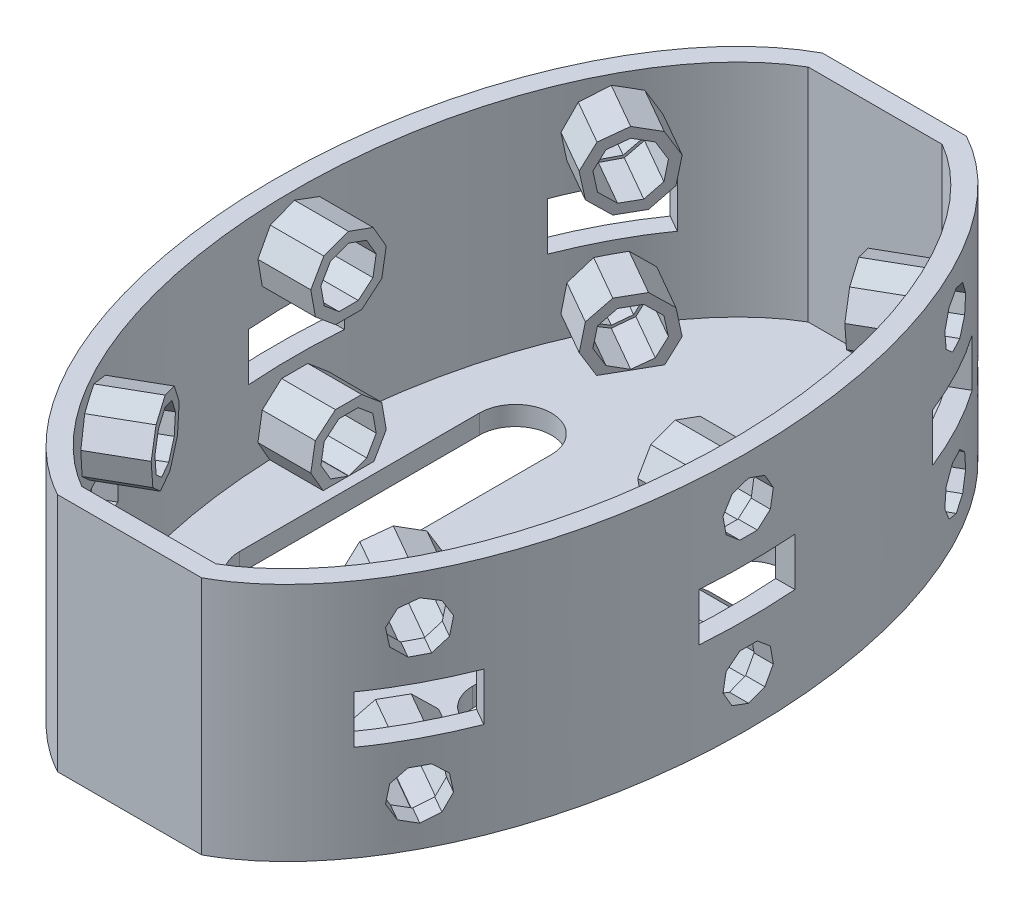
SolidWorks part; units mm, degrees
ref_plane "Front Plane" through (0, 0, 0) normal (0, 0, 1) x (1, 0, 0)
ref_plane "Top Plane" through (0, 0, 0) normal (0, 1, 0) x (1, 0, 0)
ref_plane "Right Plane" through (0, 0, 0) normal (1, 0, 0) x (0, 0, -1)
sketch "Sketch1" plane through (0, 0, 0) normal (0, 1, 0) x (1, 0, 0)
  line L0 (-15, 79.6562) -> (15, 79.6562)
  line L9 (-15, 75.1314) -> (-42.5, 27.5)
  line L10 (-42.5, 27.5) -> (-42.5, -27.5)
  line L16 (15, 75.1314) -> (-15, 75.1314)
  line L17 (-49.2865, 0) -> (49.2865, 0) construction
  line L18 (-15, 75.1314) -> (-15, 79.6562) construction
  line L19 (0, -79.6261) -> (0, -79.6562) construction
  line L20 (-15, 75.1314) -> (-18.7805, 77.3141) construction
  line L21 (-42.5, 27.5) -> (-46.1003, 29.5787) construction
  line L22 (-42.5, 27.5) -> (-46.5452, 27.5) construction
  line L23 (-18.7805, -77.3141) -> (-46.1003, -29.5787) construction
  line L24 (-42.5, -27.5) -> (-46.5452, -27.5) construction
  line L25 (-42.5, -27.5) -> (-46.1003, -29.5787) construction
  line L26 (-15, -75.1314) -> (-18.7805, -77.3141) construction
  line L27 (-15, -75.1314) -> (-15, -79.6562) construction
  line L28 (15, -75.1314) -> (-15, -75.1314)
  line L29 (-15, -75.1314) -> (-42.5, -27.5)
  line L30 (-15, -79.6562) -> (15, -79.6562)
  line L31 (18.7805, 77.3141) -> (46.1003, 29.5787) construction
  line L32 (46.5452, -27.5) -> (46.5452, 27.5) construction
  line L33 (15, -75.1314) -> (15, -79.6562) construction
  line L35 (15, -75.1314) -> (18.7805, -77.3141) construction
  line L36 (42.5, -27.5) -> (46.1003, -29.5787) construction
  line L37 (42.5, -27.5) -> (46.5452, -27.5) construction
  line L38 (18.7805, -77.3141) -> (46.1003, -29.5787) construction
  line L39 (42.5, 27.5) -> (46.5452, 27.5) construction
  line L40 (-46.5452, -27.5) -> (-46.5452, 27.5) construction
  line L41 (-18.7805, 77.3141) -> (-46.1003, 29.5787) construction
  line L42 (0, 79.6562) -> (0, -75.1314) construction
  line L43 (42.5, 27.5) -> (46.1003, 29.5787) construction
  line L44 (15, 75.1314) -> (18.7805, 77.3141) construction
  line L45 (15, 75.1314) -> (15, 79.6562) construction
  line L46 (15, -75.1314) -> (42.5, -27.5)
  line L47 (42.5, 27.5) -> (42.5, -27.5)
  line L48 (15, 75.1314) -> (42.5, 27.5)
  ellipse E0 centre (0, 0) end of major axis (0, 79.6261) minor radius 45.2865
  ellipse E1 centre (0, 0) end of major axis (0, 83.623) minor radius 49.2865 (-15, 79.6562) -> (-15, -79.6562) ccw
  ellipse E2 centre (0, 0) end of major axis (0, 83.623) minor radius 49.2865 (15, 79.6562) -> (15, -79.6562) cw
  point P7 (-46.5452, 0)
  point P15 (-42.5, 0)
  point P16 (45.2865, 0)
  point P42 (0, 79.6261)
  point P46 (-45.2865, 0)
  point P49 (0, 75.1314)
  point P50 (42.5, 0)
  point P51 (46.5452, 0)
  dimension "D1" = 55
  dimension "D3" = 150
extrude "Boss-Extrude2" add sketch "Sketch1" along normal blind 50 contours E1 L30 E2 L0
shell "Shell2" thickness 4 removed face at (0, 50, 0)
ref_plane "Plane2" through (0, 0, 0) normal (0, 1, 0) x (1, 0, 0)
sketch "Sketch3" plane through (0, 0, 0) normal (0, 1, 0) x (1, 0, 0)
  line L9 (-15, 79.6562) -> (15, 79.6562)
  line L10 (-15, 75.1314) -> (-42.5, 27.5)
  line L11 (-42.5, 27.5) -> (-42.5, -27.5)
  line L12 (15, 75.1314) -> (-15, 75.1314)
  line L13 (-49.2865, 0) -> (49.2865, 0) construction
  line L14 (-15, 75.1314) -> (-15, 79.6562) construction
  line L15 (0, -80.445) -> (0, -79.6562) construction
  line L16 (-15, 75.1314) -> (-18.7805, 77.3141) construction
  line L17 (-42.5, 27.5) -> (-46.1003, 29.5787) construction
  line L18 (-42.5, 27.5) -> (-46.5452, 27.5) construction
  line L20 (-18.7805, -77.3141) -> (-46.1003, -29.5787) construction
  line L21 (-42.5, -27.5) -> (-46.5452, -27.5) construction
  line L22 (-42.5, -27.5) -> (-46.1003, -29.5787) construction
  line L23 (-15, -75.1314) -> (-18.7805, -77.3141) construction
  line L24 (-15, -75.1314) -> (-15, -79.6562) construction
  line L27 (15, -75.1314) -> (-15, -75.1314)
  line L28 (-15, -75.1314) -> (-42.5, -27.5)
  line L29 (-15, -79.6562) -> (15, -79.6562)
  line L30 (18.7805, 77.3141) -> (46.1003, 29.5787) construction
  line L31 (46.5452, -27.5) -> (46.5452, 27.5) construction
  line L32 (15, -75.1314) -> (15, -79.6562) construction
  line L33 (15, -75.1314) -> (18.7805, -77.3141) construction
  line L34 (42.5, -27.5) -> (46.1003, -29.5787) construction
  line L35 (42.5, -27.5) -> (46.5452, -27.5) construction
  line L36 (18.7805, -77.3141) -> (46.1003, -29.5787) construction
  line L37 (42.5, 27.5) -> (46.5452, 27.5) construction
  line L38 (-46.5452, -27.5) -> (-46.5452, 27.5) construction
  line L39 (-18.7805, 77.3141) -> (-46.1003, 29.5787) construction
  line L40 (0, 79.6562) -> (0, -75.1314) construction
  line L41 (42.5, 27.5) -> (46.1003, 29.5787) construction
  line L42 (15, 75.1314) -> (18.7805, 77.3141) construction
  line L43 (15, 75.1314) -> (15, 79.6562) construction
  line L44 (15, -75.1314) -> (42.5, -27.5)
  line L45 (42.5, 27.5) -> (42.5, -27.5)
  line L46 (15, 75.1314) -> (42.5, 27.5)
  ellipse E0 centre (0, 0) end of major axis (0, 80.445) minor radius 45.7523
  ellipse E1 centre (0, 0) end of major axis (0, 83.623) minor radius 49.2865 (-15, 79.6562) -> (-15, -79.6562) ccw
  ellipse E3 centre (0, 0) end of major axis (0, 83.623) minor radius 49.2865 (15, 79.6562) -> (15, -79.6562) cw
  point P7 (-46.5452, 0)
  point P14 (-42.5, 0)
  point P15 (45.7523, 0)
  point P57 (0, 80.445)
  point P61 (-45.7523, 0)
  point P64 (0, 75.1314)
  point P65 (42.5, 0)
  point P66 (46.5452, 0)
  dimension "D1" = 55
  dimension "D2" = 150
ref_plane "Plane7" through (0, 4, 0) normal (0, 1, 0) x (1, 0, 0)
sketch "Sketch7" plane through (0, 4, 0) normal (0, 1, 0) x (1, 0, 0)
  line L5 (-24.2865, 25) -> (-24.2865, -25) construction
  line L6 (-16.7865, 25) -> (-16.7865, -25)
  line L10 (-31.7865, 25) -> (-31.7865, -25)
  line L11 (24.2865, 25) -> (24.2865, -25) construction
  line L14 (0, 79.6562) -> (0, -79.6562) construction
  line L15 (-15, 79.6562) -> (15, 79.6562) construction
  line L16 (-15, -79.6562) -> (15, -79.6562) construction
  line L17 (-49.2865, 0) -> (49.2865, 0) construction
  line L18 (16.7865, 25) -> (16.7865, -25)
  line L19 (31.7865, 25) -> (31.7865, -25)
  arc A0 (-16.7865, 25) -> (-31.7865, 25) centre (-24.2865, 25) ccw
  arc A1 (-31.7865, -25) -> (-16.7865, -25) centre (-24.2865, -25) ccw
  arc A2 (16.7865, 25) -> (31.7865, 25) centre (24.2865, 25) cw
  arc A3 (31.7865, -25) -> (16.7865, -25) centre (24.2865, -25) cw
  ellipse E0 centre (0, 0) end of major axis (0, 83.623) minor radius 49.2865 (-15, 79.6562) -> (-15, -79.6562) ccw construction
  ellipse E1 centre (0, 0) end of major axis (0, 83.623) minor radius 49.2865 (15, -79.6562) -> (15, 79.6562) ccw construction
  point P1 (-24.2865, 0)
  point P7 (0, 0)
  point P10 (24.2865, 0)
  dimension "D1" = 25
extrude "Cut-Extrude4" cut sketch "Sketch7" against normal blind 10
sketch3d "3DSketch1"
  line L0 (-15, 0, -79.6562) -> (-15, 50, -79.6562)
  line L1 (-18.7805, 0, -77.3141) -> (-18.7805, 50, -77.3141)
  line L2 (-46.1003, 0, -29.5787) -> (-46.1003, 50, -29.5787)
  line L3 (-46.5452, 0, -27.5) -> (-46.5452, 50, -27.5)
  line L4 (-46.5452, 0, 27.5) -> (-46.5452, 50, 27.5)
  line L5 (-46.1003, 0, 29.5787) -> (-46.1003, 50, 29.5787)
  line L6 (-18.7805, 0, 77.3141) -> (-18.7805, 50, 77.3141)
  line L7 (-15, 0, 79.6562) -> (-15, 50, 79.6562)
  line L8 (15, 0, 79.6562) -> (15, 50, 79.6562)
  line L9 (18.7805, 0, 77.3141) -> (18.7805, 50, 77.3141)
  line L11 (46.1003, 0, 29.5787) -> (46.1003, 50, 29.5787)
  line L12 (46.5452, 0, -27.5) -> (46.5452, 50, -27.5)
  line L13 (46.1003, 0, -29.5787) -> (46.1003, 50, -29.5787)
  line L14 (46.5452, 0, 27.5) -> (46.5452, 50, 27.5)
  line L15 (18.7805, 0, -77.3141) -> (18.7805, 50, -77.3141)
  line L16 (15, 0, -79.6562) -> (15, 50, -79.6562)
  line L17 (15, 50, -79.6562) -> (15, 0, -79.6562) construction
  spline S0 degree 3 poles (-15, 50, -79.6562) (-70.5999, 50, -49.5163) (-70.5999, 50, 49.5163) (-15, 50, 79.6562) knots 0 0 0 0 1 1 1 1 weights 1 0.536229 0.536229 1 construction
  spline S1 degree 3 poles (15, 50, -79.6562) (70.5999, 50, -49.5163) (70.5999, 50, 49.5163) (15, 50, 79.6562) knots 0 0 0 0 1 1 1 1 weights 1 0.536229 0.536229 1 construction
ref_plane "Plane8" through (-47.4776, 0, -27.1722) normal (0.8679, 0, 0.4967) x (0.4967, 0, -0.8679)
ref_plane "Plane9" through (-46.5452, 0, 0) normal (1, 0, 0) x (0, 0, -1)
ref_plane "Plane10" through (-47.4776, 0, 27.1722) normal (0.8679, 0, -0.4967) x (-0.4967, 0, -0.8679)
sketch "Sketch8" plane through (-47.4776, 0, -27.1722) normal (0.8679, 0, 0.4967) x (0.4967, 0, -0.8679)
  line L0 (57.7731, 50) -> (2.7727, 50) construction
  line L1 (2.7727, 50) -> (2.7727, 0) construction
  line L2 (2.7727, 0) -> (57.7731, 0) construction
  line L3 (57.7731, 0) -> (57.7731, 50) construction
  line L4 (30.2729, 50) -> (30.2729, 0) construction
  line L6 (40.2729, 20) -> (20.2729, 20)
  line L7 (2.7727, 25) -> (57.7731, 25) construction
  line L8 (40.2729, 20) -> (40.2729, 30)
  line L9 (40.2729, 30) -> (20.2729, 30)
  line L10 (20.2729, 20) -> (20.2729, 30)
  line L11 (40.2729, 20) -> (20.2729, 30) construction
  line L12 (40.2729, 30) -> (20.2729, 20) construction
  line L13 (30.2729, 45.3209) -> (26.8527, 44.076)
  line L14 (26.8527, 44.076) -> (25.0328, 40.924)
  line L15 (25.0328, 40.924) -> (25.6649, 37.3396)
  line L16 (25.6649, 37.3396) -> (28.453, 35)
  line L17 (28.453, 35) -> (32.0927, 35)
  line L18 (32.0927, 35) -> (34.8809, 37.3396)
  line L19 (34.8809, 37.3396) -> (35.5129, 40.924)
  line L20 (35.5129, 40.924) -> (33.6931, 44.076)
  line L21 (33.6931, 44.076) -> (30.2729, 45.3209)
  line L22 (26.8527, 5.924) -> (30.2729, 4.6791)
  line L23 (30.2729, 4.6791) -> (33.6931, 5.924)
  line L24 (33.6931, 5.924) -> (35.5129, 9.076)
  line L25 (35.5129, 9.076) -> (34.8809, 12.6604)
  line L26 (34.8809, 12.6604) -> (32.0927, 15)
  line L27 (32.0927, 15) -> (28.453, 15)
  line L28 (28.453, 15) -> (25.6649, 12.6604)
  line L29 (25.6649, 12.6604) -> (25.0328, 9.076)
  line L30 (25.0328, 9.076) -> (26.8527, 5.924)
  circle A0 centre (30.2729, 40) radius 5 construction
  circle A1 centre (30.2729, 10) radius 5 construction
  point P10 (30.2729, 25)
  dimension "D1" = 10
  dimension "D2" = 10
extrude "Cut-Extrude5" cut sketch "Sketch8" along normal blind 10 and the other way blind 10
sketch "Sketch9" plane through (-46.5452, 0, 0) normal (1, 0, 0) x (0, 0, -1)
  line L0 (27.5, 50) -> (-27.5, 50) construction
  line L1 (-27.5, 50) -> (-27.5, 0) construction
  line L2 (-27.5, 0) -> (27.5, 0) construction
  line L3 (27.5, 0) -> (27.5, 50) construction
  line L4 (0, 50) -> (0, 0) construction
  line L5 (27.5, 25) -> (-27.5, 25) construction
  line L7 (10, 30) -> (-10, 30)
  line L8 (10, 30) -> (10, 20)
  line L9 (10, 20) -> (-10, 20)
  line L10 (-10, 30) -> (-10, 20)
  line L11 (10, 30) -> (-10, 20) construction
  line L12 (10, 20) -> (-10, 30) construction
  line L13 (-1.8199, 35) -> (1.8199, 35)
  line L14 (1.8199, 35) -> (4.608, 37.3396)
  line L15 (4.608, 37.3396) -> (5.2401, 40.924)
  line L16 (5.2401, 40.924) -> (3.4202, 44.076)
  line L17 (3.4202, 44.076) -> (0, 45.3209)
  line L18 (0, 45.3209) -> (-3.4202, 44.076)
  line L19 (-3.4202, 44.076) -> (-5.2401, 40.924)
  line L20 (-5.2401, 40.924) -> (-4.608, 37.3396)
  line L21 (-4.608, 37.3396) -> (-1.8199, 35)
  line L22 (0, 4.6791) -> (3.4202, 5.924)
  line L23 (3.4202, 5.924) -> (5.2401, 9.076)
  line L24 (5.2401, 9.076) -> (4.608, 12.6604)
  line L25 (4.608, 12.6604) -> (1.8199, 15)
  line L26 (1.8199, 15) -> (-1.8199, 15)
  line L27 (-1.8199, 15) -> (-4.608, 12.6604)
  line L28 (-4.608, 12.6604) -> (-5.2401, 9.076)
  line L29 (-5.2401, 9.076) -> (-3.4202, 5.924)
  line L30 (-3.4202, 5.924) -> (0, 4.6791)
  circle A0 centre (0, 40) radius 5 construction
  circle A1 centre (0, 10) radius 5 construction
  point P13 (0, 25)
  dimension "D1" = 10
  dimension "D2" = 10
extrude "Cut-Extrude6" cut sketch "Sketch9" against normal blind 10 and the other way blind 10
sketch "Sketch11" plane through (-47.4776, 0, 27.1722) normal (0.8679, 0, -0.4967) x (-0.4967, 0, -0.8679)
  line L0 (-2.7727, 50) -> (-57.7731, 50) construction
  line L1 (-57.7731, 50) -> (-57.7731, 0) construction
  line L2 (-57.7731, 0) -> (-2.7727, 0) construction
  line L3 (-2.7727, 0) -> (-2.7727, 50) construction
  line L4 (-30.2729, 50) -> (-30.2729, 0) construction
  line L5 (-2.7727, 25) -> (-57.7731, 25) construction
  line L7 (-40.2729, 20) -> (-20.2729, 20)
  line L8 (-40.2729, 20) -> (-40.2729, 30)
  line L9 (-40.2729, 30) -> (-20.2729, 30)
  line L10 (-20.2729, 20) -> (-20.2729, 30)
  line L11 (-40.2729, 20) -> (-20.2729, 30) construction
  line L12 (-40.2729, 30) -> (-20.2729, 20) construction
  line L13 (-34.8809, 37.3396) -> (-32.0927, 35)
  line L14 (-32.0927, 35) -> (-28.453, 35)
  line L15 (-28.453, 35) -> (-25.6649, 37.3396)
  line L16 (-25.6649, 37.3396) -> (-25.0328, 40.924)
  line L17 (-25.0328, 40.924) -> (-26.8527, 44.076)
  line L18 (-26.8527, 44.076) -> (-30.2729, 45.3209)
  line L19 (-30.2729, 45.3209) -> (-33.6931, 44.076)
  line L20 (-33.6931, 44.076) -> (-35.5129, 40.924)
  line L21 (-35.5129, 40.924) -> (-34.8809, 37.3396)
  line L22 (-35.5129, 9.076) -> (-33.6931, 5.924)
  line L23 (-33.6931, 5.924) -> (-30.2729, 4.6791)
  line L24 (-30.2729, 4.6791) -> (-26.8527, 5.924)
  line L25 (-26.8527, 5.924) -> (-25.0328, 9.076)
  line L26 (-25.0328, 9.076) -> (-25.6649, 12.6604)
  line L27 (-25.6649, 12.6604) -> (-28.453, 15)
  line L28 (-28.453, 15) -> (-32.0927, 15)
  line L29 (-32.0927, 15) -> (-34.8809, 12.6604)
  line L30 (-34.8809, 12.6604) -> (-35.5129, 9.076)
  circle A0 centre (-30.2729, 40) radius 5 construction
  circle A1 centre (-30.2729, 10) radius 5 construction
  point P12 (-30.2729, 25)
  dimension "D1" = 10
  dimension "D2" = 10
extrude "Cut-Extrude7" cut sketch "Sketch11" against normal blind 10 and the other way blind 10
mirror "Mirror1" about plane through (0, 0, 0) normal (1, 0, 0) of "Cut-Extrude7", "Cut-Extrude6", "Cut-Extrude5"
sketch "Sketch12" plane through (-47.4776, 0, 27.1722) normal (0.8679, 0, -0.4967) x (-0.4967, 0, -0.8679)
  line L36 (-2.7727, 50) -> (-57.7731, 50) construction
  line L37 (-57.7731, 50) -> (-57.7731, 0) construction
  line L38 (-57.7731, 0) -> (-2.7727, 0) construction
  line L39 (-2.7727, 0) -> (-2.7727, 50) construction
  line L40 (-30.2729, 50) -> (-30.2729, 0) construction
  line L41 (-26.8527, 44.076) -> (-33.4868, 36.1698) construction
  line L42 (-33.6931, 44.076) -> (-27.0589, 36.1698) construction
  line L43 (-25.0328, 40.924) -> (-35.1969, 39.1318) construction
  line L44 (-28.453, 15) -> (-31.983, 5.3015) construction
  line L45 (-37.1849, 36.0093) -> (-33.0027, 32.5)
  line L46 (-33.0027, 32.5) -> (-27.5431, 32.5)
  line L47 (-27.5431, 32.5) -> (-23.3608, 36.0093)
  line L48 (-23.3608, 36.0093) -> (-22.4128, 41.3859)
  line L49 (-22.4128, 41.3859) -> (-25.1426, 46.1141)
  line L50 (-25.1426, 46.1141) -> (-30.2729, 47.9813)
  line L51 (-30.2729, 47.9813) -> (-35.4032, 46.1141)
  line L52 (-35.4032, 46.1141) -> (-38.133, 41.3859)
  line L53 (-38.133, 41.3859) -> (-37.1849, 36.0093)
  line L54 (-25.6649, 12.6604) -> (-34.603, 7.5) construction
  line L55 (-25.0328, 9.076) -> (-35.1969, 10.8682) construction
  line L57 (-35.4032, 3.8859) -> (-30.2729, 2.0187)
  line L58 (-30.2729, 2.0187) -> (-25.1426, 3.8859)
  line L59 (-25.1426, 3.8859) -> (-22.4128, 8.6141)
  line L60 (-22.4128, 8.6141) -> (-23.3608, 13.9907)
  line L61 (-23.3608, 13.9907) -> (-27.5431, 17.5)
  line L62 (-27.5431, 17.5) -> (-33.0027, 17.5)
  line L63 (-33.0027, 17.5) -> (-37.1849, 13.9907)
  line L64 (-37.1849, 13.9907) -> (-38.133, 8.6141)
  line L65 (-38.133, 8.6141) -> (-35.4032, 3.8859)
  line L66 (-26.5107, 44.4836) -> (-30.2729, 45.853)
  line L67 (-30.2729, 45.853) -> (-34.0351, 44.4836)
  line L68 (-34.0351, 44.4836) -> (-36.0369, 41.0164)
  line L69 (-36.0369, 41.0164) -> (-35.3417, 37.0735)
  line L70 (-35.3417, 37.0735) -> (-32.2747, 34.5)
  line L71 (-32.2747, 34.5) -> (-28.271, 34.5)
  line L72 (-28.271, 34.5) -> (-25.204, 37.0735)
  line L73 (-25.204, 37.0735) -> (-24.5088, 41.0164)
  line L74 (-24.5088, 41.0164) -> (-26.5107, 44.4836)
  line L75 (-34.0351, 5.5164) -> (-30.2729, 4.147)
  line L76 (-30.2729, 4.147) -> (-26.5107, 5.5164)
  line L77 (-26.5107, 5.5164) -> (-24.5088, 8.9836)
  line L78 (-24.5088, 8.9836) -> (-25.204, 12.9265)
  line L79 (-25.204, 12.9265) -> (-28.271, 15.5)
  line L80 (-28.271, 15.5) -> (-32.2747, 15.5)
  line L81 (-32.2747, 15.5) -> (-35.3417, 12.9265)
  line L82 (-35.3417, 12.9265) -> (-36.0369, 8.9836)
  line L83 (-36.0369, 8.9836) -> (-34.0351, 5.5164)
  circle A0 centre (-30.2729, 40) radius 7.5 construction
  circle A1 centre (-30.2729, 10) radius 7.5 construction
  circle A2 centre (-30.2729, 40) radius 5.5 construction
  circle A3 centre (-30.2729, 10) radius 5.5 construction
extrude "Boss-Extrude4" add sketch "Sketch12" along normal blind 10 and the other way blind 3
sketch "Sketch13" plane through (-47.4776, 0, -27.1722) normal (0.8679, 0, 0.4967) x (0.4967, 0, -0.8679)
  line L0 (57.7731, 50) -> (2.7727, 50) construction
  line L1 (2.7727, 50) -> (2.7727, 0) construction
  line L2 (2.7727, 0) -> (57.7731, 0) construction
  line L3 (57.7731, 0) -> (57.7731, 50) construction
  line L4 (30.2729, 50) -> (30.2729, 0) construction
  line L33 (33.6931, 44.076) -> (27.0589, 36.1698) construction
  line L34 (34.8809, 37.3396) -> (25.9427, 42.5) construction
  line L35 (35.5129, 40.924) -> (25.3488, 39.1318) construction
  line L36 (32.0927, 15) -> (28.5628, 5.3015) construction
  line L37 (35.5129, 9.076) -> (25.3488, 10.8682) construction
  line L39 (30.2729, 4.147) -> (34.0351, 5.5164)
  line L40 (34.0351, 5.5164) -> (36.0369, 8.9836)
  line L41 (36.0369, 8.9836) -> (35.3417, 12.9265)
  line L42 (35.3417, 12.9265) -> (32.2747, 15.5)
  line L43 (32.2747, 15.5) -> (28.271, 15.5)
  line L44 (28.271, 15.5) -> (25.204, 12.9265)
  line L45 (25.204, 12.9265) -> (24.5088, 8.9836)
  line L46 (24.5088, 8.9836) -> (26.5107, 5.5164)
  line L47 (26.5107, 5.5164) -> (30.2729, 4.147)
  line L48 (25.1426, 3.8859) -> (30.2729, 2.0187)
  line L49 (30.2729, 2.0187) -> (35.4032, 3.8859)
  line L50 (35.4032, 3.8859) -> (38.133, 8.6141)
  line L51 (38.133, 8.6141) -> (37.1849, 13.9907)
  line L52 (37.1849, 13.9907) -> (33.0027, 17.5)
  line L53 (33.0027, 17.5) -> (27.5431, 17.5)
  line L54 (27.5431, 17.5) -> (23.3608, 13.9907)
  line L55 (23.3608, 13.9907) -> (22.4128, 8.6141)
  line L56 (22.4128, 8.6141) -> (25.1426, 3.8859)
  line L57 (28.271, 34.4843) -> (32.2747, 34.4843)
  line L58 (32.2747, 34.4843) -> (35.3417, 37.0578)
  line L59 (35.3417, 37.0578) -> (36.0369, 41.0006)
  line L60 (36.0369, 41.0006) -> (34.0351, 44.4679)
  line L61 (34.0351, 44.4679) -> (30.2729, 45.8373)
  line L62 (30.2729, 45.8373) -> (26.5107, 44.4679)
  line L63 (26.5107, 44.4679) -> (24.5088, 41.0006)
  line L64 (24.5088, 41.0006) -> (25.204, 37.0578)
  line L65 (25.204, 37.0578) -> (28.271, 34.4843)
  line L66 (27.5431, 32.4843) -> (33.0027, 32.4843)
  line L67 (33.0027, 32.4843) -> (37.1849, 35.9936)
  line L68 (37.1849, 35.9936) -> (38.133, 41.3702)
  line L69 (38.133, 41.3702) -> (35.4032, 46.0983)
  line L70 (35.4032, 46.0983) -> (30.2729, 47.9656)
  line L71 (30.2729, 47.9656) -> (25.1426, 46.0983)
  line L72 (25.1426, 46.0983) -> (22.4128, 41.3702)
  line L73 (22.4128, 41.3702) -> (23.3608, 35.9936)
  line L74 (23.3608, 35.9936) -> (27.5431, 32.4843)
  circle A0 centre (30.2729, 10) radius 5.5 construction
  circle A1 centre (30.2729, 10) radius 7.5 construction
  circle A2 centre (30.2729, 39.9843) radius 5.5 construction
  circle A3 centre (30.2729, 39.9843) radius 7.5 construction
extrude "Boss-Extrude5" add sketch "Sketch13" along normal blind 10 and the other way blind 3
sketch "Sketch14" plane through (-46.5452, 0, 0) normal (1, 0, 0) x (0, 0, -1)
  line L0 (27.5, 50) -> (-27.5, 50) construction
  line L1 (-27.5, 50) -> (-27.5, 0) construction
  line L2 (-27.5, 0) -> (27.5, 0) construction
  line L3 (27.5, 0) -> (27.5, 50) construction
  line L4 (0, 50) -> (0, 45.3209) construction
  line L41 (0, 4.6791) -> (0, 0) construction
  line L42 (0, 35) -> (0, 15) construction
  line L43 (0, 45.3209) -> (0, 35) construction
  line L44 (0, 15) -> (0, 4.6791) construction
  line L46 (-5.0608, 37.2201) -> (-1.9868, 34.655)
  line L47 (-1.9868, 34.655) -> (2.0169, 34.6659)
  line L48 (2.0169, 34.6659) -> (5.0768, 37.2479)
  line L49 (5.0768, 37.2479) -> (5.7613, 41.1926)
  line L50 (5.7613, 41.1926) -> (3.7499, 44.6544)
  line L51 (3.7499, 44.6544) -> (-0.016, 46.0134)
  line L52 (-0.016, 46.0134) -> (-3.7745, 44.6338)
  line L53 (-3.7745, 44.6338) -> (-5.7668, 41.161)
  line L54 (-5.7668, 41.161) -> (-5.0608, 37.2201)
  line L55 (-6.9011, 36.1509) -> (-2.7092, 32.653)
  line L56 (-2.7092, 32.653) -> (2.7503, 32.6679)
  line L57 (2.7503, 32.6679) -> (6.9229, 36.1887)
  line L58 (6.9229, 36.1887) -> (7.8563, 41.5679)
  line L59 (7.8563, 41.5679) -> (5.1135, 46.2885)
  line L60 (5.1135, 46.2885) -> (-0.0219, 48.1417)
  line L61 (-0.0219, 48.1417) -> (-5.147, 46.2604)
  line L62 (-5.147, 46.2604) -> (-7.8638, 41.5249)
  line L63 (-7.8638, 41.5249) -> (-6.9011, 36.1509)
  line L64 (-7.8601, 8.4537) -> (-5.1303, 3.7255)
  line L65 (-5.1303, 3.7255) -> (-0.0001, 1.8582)
  line L66 (-0.0001, 1.8582) -> (5.1303, 3.7255)
  line L67 (5.1303, 3.7255) -> (7.8601, 8.4536)
  line L68 (7.8601, 8.4536) -> (6.9121, 13.8302)
  line L69 (6.9121, 13.8302) -> (2.7298, 17.3395)
  line L70 (2.7298, 17.3395) -> (-2.7297, 17.3396)
  line L71 (-2.7297, 17.3396) -> (-6.912, 13.8303)
  line L72 (-6.912, 13.8303) -> (-7.8601, 8.4537)
  line L73 (-3.7429, 5.3398) -> (0.0251, 3.9866)
  line L74 (0.0251, 3.9866) -> (3.7815, 5.3721)
  line L75 (3.7815, 5.3721) -> (5.7684, 8.848)
  line L76 (5.7684, 8.848) -> (5.0562, 12.7878)
  line L77 (5.0562, 12.7878) -> (1.9782, 15.3481)
  line L78 (1.9782, 15.3481) -> (-2.0254, 15.3309)
  line L79 (-2.0254, 15.3309) -> (-5.0814, 12.7442)
  line L80 (-5.0814, 12.7442) -> (-5.7596, 8.7984)
  line L81 (-5.7596, 8.7984) -> (-3.7429, 5.3398)
  circle A0 centre (0, 40.1604) radius 5.5 construction
  circle A1 centre (0, 40.1604) radius 7.5 construction
  circle A2 centre (0, 9.8396) radius 7.5 construction
  circle A3 centre (0, 9.8396) radius 5.5 construction
extrude "Boss-Extrude6" add sketch "Sketch14" along normal blind 12.5 and the other way blind 2
ref_plane "Plane11" through (47.4776, 0, 27.1722) normal (-0.8679, 0, -0.4967) x (-0.4967, 0, 0.8679)
ref_plane "Plane12" through (46.5452, 0, 0) normal (-1, 0, 0) x (0, 0, 1)
ref_plane "Plane13" through (47.4776, 0, -27.1722) normal (0.8679, 0, -0.4967) x (-0.4967, 0, -0.8679)
sketch "Sketch15" plane through (47.4776, 0, 27.1722) normal (-0.8679, 0, -0.4967) x (-0.4967, 0, 0.8679)
  line L12 (30.2729, 45.3209) -> (30.2729, 35) construction
  line L13 (30.2729, 15) -> (30.2729, 4.6791) construction
  line L14 (30.2729, 15) -> (30.2729, 35) construction
  line L15 (30.2729, 45.3209) -> (30.2729, 49.8304) construction
  line L16 (30.2729, 4.6791) -> (30.2729, 0) construction
  line L18 (25.204, 37.234) -> (28.271, 34.6604)
  line L19 (28.271, 34.6604) -> (32.2747, 34.6604)
  line L20 (32.2747, 34.6604) -> (35.3417, 37.234)
  line L21 (35.3417, 37.234) -> (36.0369, 41.1768)
  line L22 (36.0369, 41.1768) -> (34.0351, 44.6441)
  line L23 (34.0351, 44.6441) -> (30.2729, 46.0134)
  line L24 (30.2729, 46.0134) -> (26.5107, 44.6441)
  line L25 (26.5107, 44.6441) -> (24.5088, 41.1768)
  line L26 (24.5088, 41.1768) -> (25.204, 37.234)
  line L27 (23.3608, 36.1698) -> (27.5431, 32.6604)
  line L28 (27.5431, 32.6604) -> (33.0027, 32.6604)
  line L29 (33.0027, 32.6604) -> (37.1849, 36.1698)
  line L30 (37.1849, 36.1698) -> (38.133, 41.5464)
  line L31 (38.133, 41.5464) -> (35.4032, 46.2745)
  line L32 (35.4032, 46.2745) -> (30.2729, 48.1418)
  line L33 (30.2729, 48.1418) -> (25.1426, 46.2745)
  line L34 (25.1426, 46.2745) -> (22.4128, 41.5464)
  line L35 (22.4128, 41.5464) -> (23.3608, 36.1698)
  line L36 (24.5088, 8.8232) -> (26.5107, 5.3559)
  line L37 (26.5107, 5.3559) -> (30.2729, 3.9866)
  line L38 (30.2729, 3.9866) -> (34.0351, 5.3559)
  line L39 (34.0351, 5.3559) -> (36.0369, 8.8232)
  line L40 (36.0369, 8.8232) -> (35.3417, 12.766)
  line L41 (35.3417, 12.766) -> (32.2747, 15.3396)
  line L42 (32.2747, 15.3396) -> (28.271, 15.3396)
  line L43 (28.271, 15.3396) -> (25.204, 12.766)
  line L44 (25.204, 12.766) -> (24.5088, 8.8232)
  line L45 (22.4128, 8.4536) -> (25.1426, 3.7255)
  line L46 (25.1426, 3.7255) -> (30.2729, 1.8582)
  line L47 (30.2729, 1.8582) -> (35.4032, 3.7255)
  line L48 (35.4032, 3.7255) -> (38.133, 8.4536)
  line L49 (38.133, 8.4536) -> (37.1849, 13.8302)
  line L50 (37.1849, 13.8302) -> (33.0027, 17.3396)
  line L51 (33.0027, 17.3396) -> (27.5431, 17.3396)
  line L52 (27.5431, 17.3396) -> (23.3608, 13.8302)
  line L53 (23.3608, 13.8302) -> (22.4128, 8.4536)
  circle A0 centre (30.2729, 40.1604) radius 5.5 construction
  circle A1 centre (30.2729, 40.1604) radius 7.5 construction
  circle A2 centre (30.2729, 9.8396) radius 5.5 construction
  circle A3 centre (30.2729, 9.8396) radius 7.5 construction
  point P1 (0, 0)
  point P2 (0, 0)
  point P36 (0, 0)
  point P57 (0, 0)
extrude "Boss-Extrude7" add sketch "Sketch15" along normal blind 10 and the other way blind 3
sketch "Sketch16" plane through (46.5452, 0, 0) normal (-1, 0, 0) x (0, 0, 1)
  line L12 (0, 45.3209) -> (0, 35) construction
  line L13 (0, 4.6791) -> (0, 15) construction
  line L14 (0, 35) -> (0, 15) construction
  line L15 (0, 45.3209) -> (0, 49.3861) construction
  line L16 (0, 4.6791) -> (0, -0.5773) construction
  line L18 (-5.7641, 8.8232) -> (-3.7622, 5.3559)
  line L19 (-3.7622, 5.3559) -> (0, 3.9866)
  line L20 (0, 3.9866) -> (3.7622, 5.3559)
  line L21 (3.7622, 5.3559) -> (5.7641, 8.8232)
  line L22 (5.7641, 8.8232) -> (5.0688, 12.766)
  line L23 (5.0688, 12.766) -> (2.0018, 15.3396)
  line L24 (2.0018, 15.3396) -> (-2.0018, 15.3396)
  line L25 (-2.0018, 15.3396) -> (-5.0688, 12.766)
  line L26 (-5.0688, 12.766) -> (-5.7641, 8.8232)
  line L27 (-7.8601, 8.4536) -> (-5.1303, 3.7255)
  line L28 (-5.1303, 3.7255) -> (0, 1.8582)
  line L29 (0, 1.8582) -> (5.1303, 3.7255)
  line L30 (5.1303, 3.7255) -> (7.8601, 8.4536)
  line L31 (7.8601, 8.4536) -> (6.912, 13.8302)
  line L32 (6.912, 13.8302) -> (2.7298, 17.3396)
  line L33 (2.7298, 17.3396) -> (-2.7298, 17.3396)
  line L34 (-2.7298, 17.3396) -> (-6.912, 13.8302)
  line L35 (-6.912, 13.8302) -> (-7.8601, 8.4536)
  line L36 (-6.912, 36.1698) -> (-2.7298, 32.6604)
  line L37 (-2.7298, 32.6604) -> (2.7298, 32.6604)
  line L38 (2.7298, 32.6604) -> (6.912, 36.1698)
  line L39 (6.912, 36.1698) -> (7.8601, 41.5464)
  line L40 (7.8601, 41.5464) -> (5.1303, 46.2745)
  line L41 (5.1303, 46.2745) -> (0, 48.1418)
  line L42 (0, 48.1418) -> (-5.1303, 46.2745)
  line L43 (-5.1303, 46.2745) -> (-7.8601, 41.5464)
  line L44 (-7.8601, 41.5464) -> (-6.912, 36.1698)
  line L45 (-5.0688, 37.234) -> (-2.0018, 34.6604)
  line L46 (-2.0018, 34.6604) -> (2.0018, 34.6604)
  line L47 (2.0018, 34.6604) -> (5.0688, 37.234)
  line L48 (5.0688, 37.234) -> (5.7641, 41.1768)
  line L49 (5.7641, 41.1768) -> (3.7622, 44.6441)
  line L50 (3.7622, 44.6441) -> (0, 46.0134)
  line L51 (0, 46.0134) -> (-3.7622, 44.6441)
  line L52 (-3.7622, 44.6441) -> (-5.7641, 41.1768)
  line L53 (-5.7641, 41.1768) -> (-5.0688, 37.234)
  circle A0 centre (0, 9.8396) radius 5.5 construction
  circle A1 centre (0, 9.8396) radius 7.5 construction
  circle A2 centre (0, 40.1604) radius 7.5 construction
  circle A3 centre (0, 40.1604) radius 5.5 construction
  point P37 (0, 0)
  point P58 (0, 0)
  point P59 (0, 0)
  point P60 (0, 0)
extrude "Boss-Extrude8" add sketch "Sketch16" along normal blind 12.5 and the other way blind 2
sketch "Sketch17" plane through (47.4776, 0, -27.1722) normal (0.8679, 0, -0.4967) x (-0.4967, 0, -0.8679)
  line L12 (30.2729, 4.6791) -> (30.2729, 15) construction
  line L13 (30.2729, 15) -> (30.2729, 35) construction
  line L14 (30.2729, 35) -> (30.2729, 45.3209) construction
  line L15 (30.2729, 45.3209) -> (30.2729, 50) construction
  line L16 (61.6836, 50) -> (-76.5951, 50) construction
  line L17 (30.2729, 4.6791) -> (30.2729, 0) construction
  line L18 (-76.5951, 0) -> (61.6836, 0) construction
  line L20 (36.0369, 8.8232) -> (35.3417, 12.766)
  line L21 (35.3417, 12.766) -> (32.2747, 15.3396)
  line L22 (32.2747, 15.3396) -> (28.271, 15.3396)
  line L23 (28.271, 15.3396) -> (25.204, 12.766)
  line L24 (25.204, 12.766) -> (24.5088, 8.8232)
  line L25 (24.5088, 8.8232) -> (26.5107, 5.3559)
  line L26 (26.5107, 5.3559) -> (30.2729, 3.9866)
  line L27 (30.2729, 3.9866) -> (34.0351, 5.3559)
  line L28 (34.0351, 5.3559) -> (36.0369, 8.8232)
  line L29 (38.133, 8.4536) -> (37.1849, 13.8302)
  line L30 (37.1849, 13.8302) -> (33.0027, 17.3396)
  line L31 (33.0027, 17.3396) -> (27.5431, 17.3396)
  line L32 (27.5431, 17.3396) -> (23.3608, 13.8302)
  line L33 (23.3608, 13.8302) -> (22.4128, 8.4536)
  line L34 (22.4128, 8.4536) -> (25.1426, 3.7255)
  line L35 (25.1426, 3.7255) -> (30.2729, 1.8582)
  line L36 (30.2729, 1.8582) -> (35.4032, 3.7255)
  line L37 (35.4032, 3.7255) -> (38.133, 8.4536)
  line L38 (30.2729, 46.0134) -> (26.5107, 44.6441)
  line L39 (26.5107, 44.6441) -> (24.5088, 41.1768)
  line L40 (24.5088, 41.1768) -> (25.204, 37.234)
  line L41 (25.204, 37.234) -> (28.271, 34.6604)
  line L42 (28.271, 34.6604) -> (32.2747, 34.6604)
  line L43 (32.2747, 34.6604) -> (35.3417, 37.234)
  line L44 (35.3417, 37.234) -> (36.0369, 41.1768)
  line L45 (36.0369, 41.1768) -> (34.0351, 44.6441)
  line L46 (34.0351, 44.6441) -> (30.2729, 46.0134)
  line L47 (30.2729, 48.1418) -> (25.1426, 46.2745)
  line L48 (25.1426, 46.2745) -> (22.4128, 41.5464)
  line L49 (22.4128, 41.5464) -> (23.3608, 36.1698)
  line L50 (23.3608, 36.1698) -> (27.5431, 32.6604)
  line L51 (27.5431, 32.6604) -> (33.0027, 32.6604)
  line L52 (33.0027, 32.6604) -> (37.1849, 36.1698)
  line L53 (37.1849, 36.1698) -> (38.133, 41.5464)
  line L54 (38.133, 41.5464) -> (35.4032, 46.2745)
  line L55 (35.4032, 46.2745) -> (30.2729, 48.1418)
  circle A0 centre (30.2729, 9.8396) radius 5.5 construction
  circle A1 centre (30.2729, 9.8396) radius 7.5 construction
  circle A2 centre (30.2729, 40.1604) radius 5.5 construction
  circle A3 centre (30.2729, 40.1604) radius 7.5 construction
  point P40 (0, 0)
  point P61 (0, 0)
  point P62 (0, 0)
  point P63 (0, 0)
extrude "Boss-Extrude9" add sketch "Sketch17" against normal blind 10 and the other way blind 3
